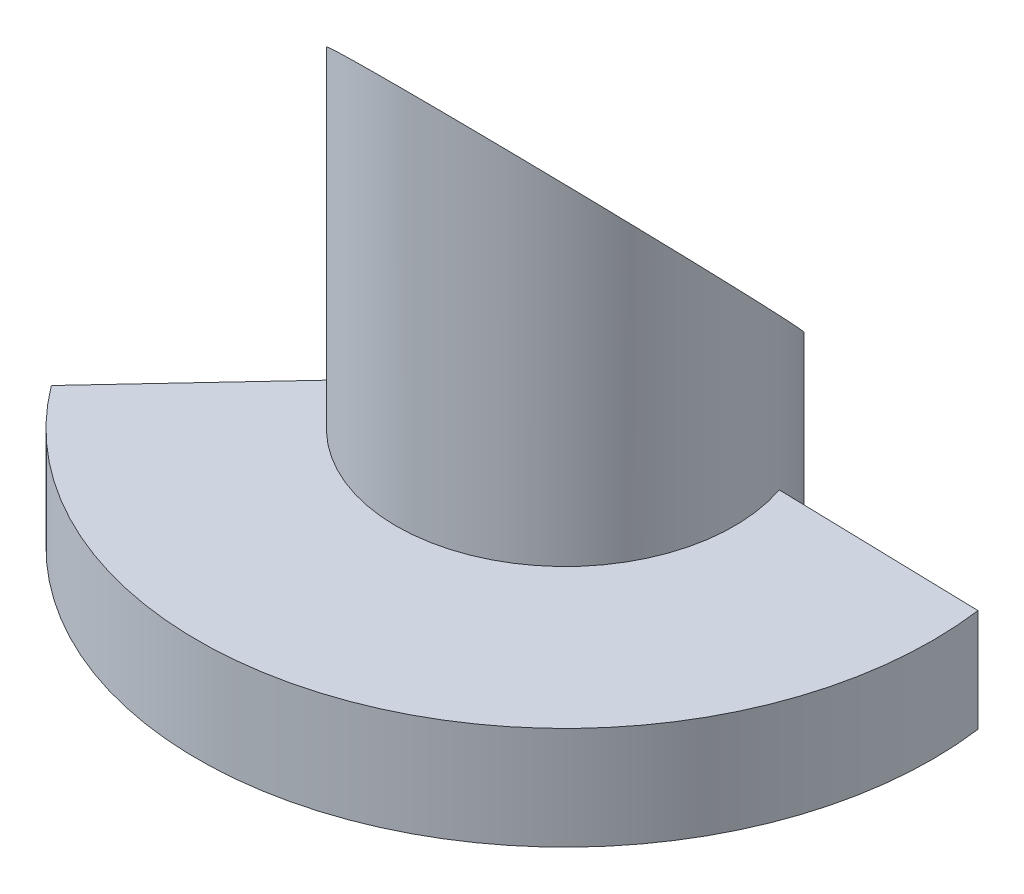
SolidWorks part; units mm, degrees
ref_plane "Front Plane" through (0, 0, 0) normal (0, 0, 1) x (1, 0, 0)
ref_plane "Top Plane" through (0, 0, 0) normal (0, 1, 0) x (1, 0, 0)
ref_plane "Right Plane" through (0, 0, 0) normal (1, 0, 0) x (0, 0, -1)
sketch "Sketch1" plane through (0, 0, 0) normal (0, 1, 0) x (1, 0, 0)
  line L0 (-10.4824, -4.7297) -> (-20.0368, -14.9508)
  line L1 (10.8967, 3.6758) -> (24.7782, 3.3225)
  circle A0 centre (0, 0) radius 25
  circle A1 centre (0, 0) radius 11.5
  point P8 (9.9492, 3.3225)
  point P9 (-9.5709, -4.3184)
  dimension "D1" = 23
  dimension "D2" = 50
extrude "Boss-Extrude1" add sketch "Sketch1" along normal blind 7 contours A1 | A1 L0 A0 L1 region at (5.068, 0, 12.5439) region at (0, 0, 0)
sketch "Sketch2" plane through (0, 7, 0) normal (0, 1, 0) x (1, 0, 0)
  circle A0 centre (0, 0) radius 11.5
extrude "Boss-Extrude2" add sketch "Sketch2" along normal blind 26
sketch "Sketch5" plane through (0, 0, 0) normal (1, 0, 0) x (0, 0, -1)
  line L0 (-11.5, 33) -> (11.5, 9.1828)
  line L1 (11.5, 9.1828) -> (-11.5, 9.1828)
  line L2 (-11.5, 9.1828) -> (-11.5, 33)
  line L3 (11.5, 0) -> (11.5, 33) construction
  line L4 (-11.5, 33) -> (11.5, 33)
  line L5 (11.5, 33) -> (11.5, 9.1828)
  dimension "D1" = 90
  dimension "D2" = 46
extrude "Cut-Extrude1" cut sketch "Sketch5" against normal blind 26 and the other way blind 26 contours L5 L4 L0 region at (0, 25.0609, -3.8333)
